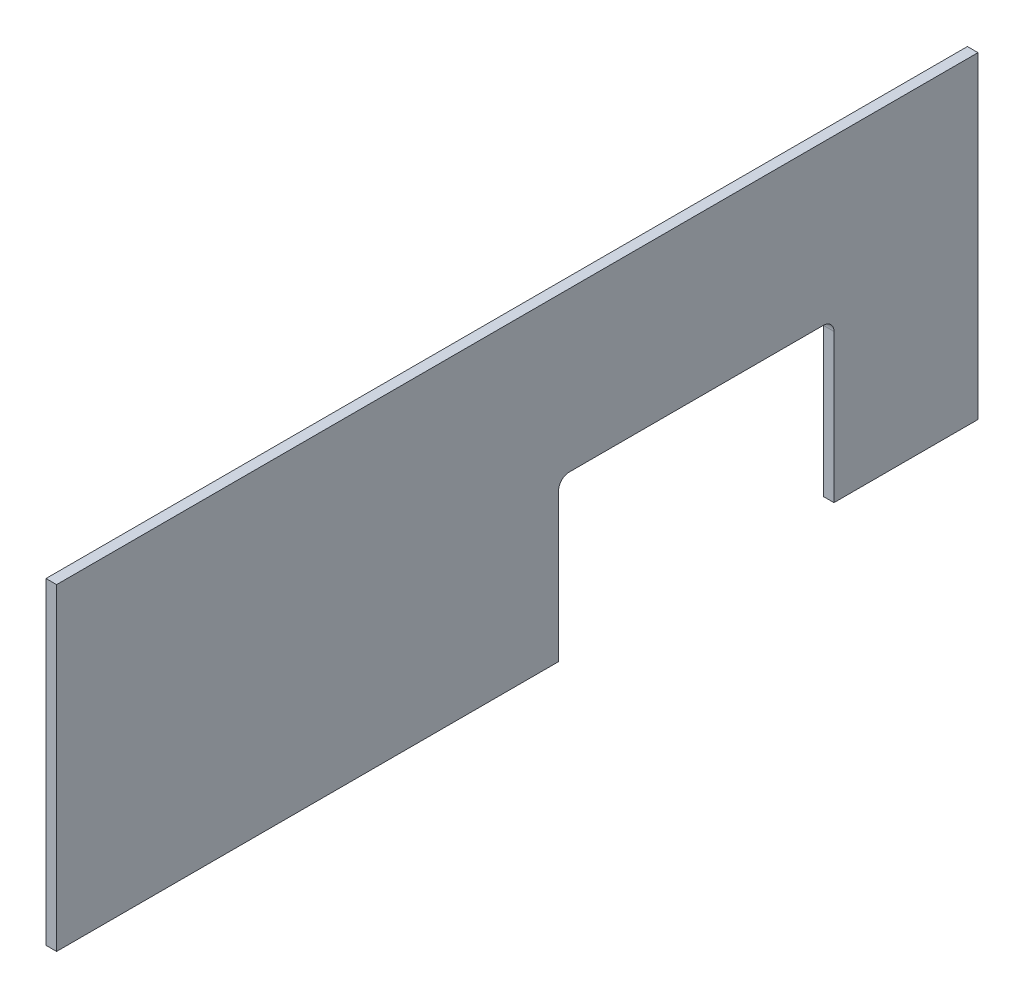
SolidWorks part; units mm, degrees
ref_plane "Front Plane" through (0, 0, 0) normal (0, 0, 1) x (1, 0, 0)
ref_plane "Top Plane" through (0, 0, 0) normal (0, 1, 0) x (1, 0, 0)
ref_plane "Right Plane" through (0, 0, 0) normal (1, 0, 0) x (0, 0, -1)
sketch "Sketch1" plane through (0, 0, 0) normal (1, 0, 0) x (0, 0, -1)
  line L1 (-43.5, -15) -> (43.5, -15)
  line L2 (-43.5, -15) -> (-43.5, 15)
  line L3 (-43.5, 15) -> (43.5, 15)
  line L4 (43.5, -15) -> (43.5, 15)
  line L5 (-43.5, -15) -> (43.5, 15) construction
  line L6 (-43.5, 15) -> (43.5, -15) construction
  line L7 (3.9, -15) -> (29.9, -15)
  line L8 (3.9, -15) -> (3.9, 0)
  line L9 (3.9, 0) -> (29.9, 0)
  line L10 (29.9, -15) -> (29.9, 0)
  point P0 (0, 0)
  dimension "D1" = 30
  dimension "D2" = 87
  dimension "D3" = 26
  dimension "D4" = 15
  dimension "D5" = 13.6
extrude "Boss-Extrude1" add sketch "Sketch1" along normal blind 1 contours L10 L1 L4 L3 L2 L8 L9 region at (0, 1.3176, 2.9689)
fillet "Fillet1" radius 1 2 edges at (0.5, 0, -29.9) (0.5, 0, -3.9)
